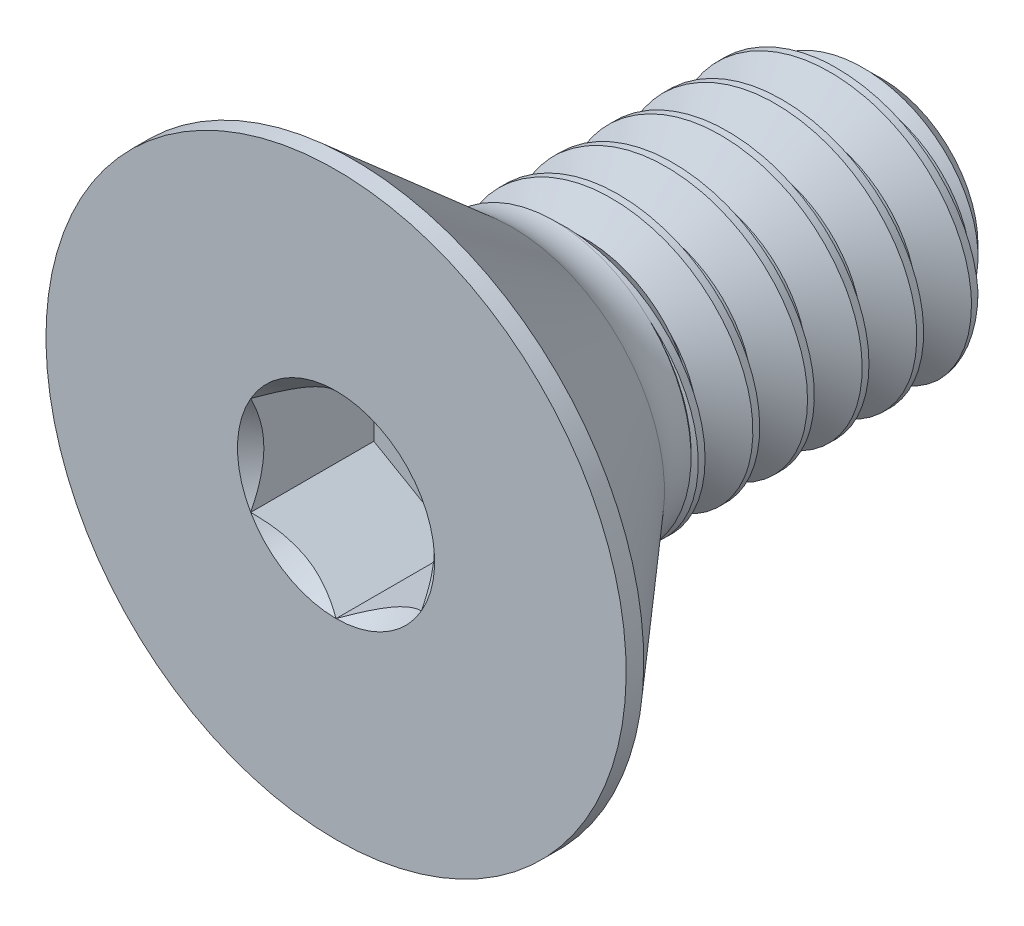
SolidWorks part; units mm, degrees
material "AISI 304"
ref_plane "Front" through (0, 0, 0) normal (0, 0, 1) x (1, 0, 0)
ref_plane "Top" through (0, 0, 0) normal (0, 1, 0) x (1, 0, 0)
ref_plane "Right" through (0, 0, 0) normal (1, 0, 0) x (0, 0, -1)
sketch "Sketch1" plane through (0, 0, 0) normal (1, 0, 0) x (0, 0, -1)
  line L0 (0, 6.7437) -> (0.4089, 6.7437) construction
  line L1 (0.4089, 6.7437) -> (4.0894, 3.5443) construction
  line L2 (0, 3.175) -> (12.7, 3.175)
  line L3 (12.7, 3.175) -> (12.7, 0)
  line L4 (12.7, 0) -> (0, 0)
  line L5 (0, 0) -> (0, 6.7437) construction
  line L6 (0, 6.7437) -> (0, -6.7437) construction
  line L7 (12.7, 3.175) -> (12.7, -3.175) construction
  line L8 (0, -6.7437) -> (0.4089, -6.7437) construction
  line L9 (0.4089, -6.7437) -> (4.0894, -3.5443) construction
  line L11 (0, 3.175) -> (0, 0)
  line L12 (5.0772, 3.175) -> (5.0772, 0) construction
  arc A1 (4.0894, 3.5443) -> (5.0772, 3.175) centre (5.0772, 4.6807) ccw construction
  dimension "D1" = 0.4089
revolve "Revolve1" add sketch "Sketch1" angle 360 mid plane about L4
sketch "Sketch3" plane through (0, 0, -12.7) normal (0, 0, -1) x (-1, 0, 0)
  circle A0 centre (0, 0) radius 3.175
curve "Helix/Spiral1" pitch 1.27 height 12.7 radius 3.175 centre (0, 0, -12.7) axis (0, 0, 1) start towards (0, 1, 0)
sketch "Sketch2" plane through (0, 0, 0) normal (1, 0, 0) x (0, 0, -1)
  line L0 (12.7, 3.175) -> (13.8113, 3.175)
  line L1 (13.8113, 3.175) -> (13.335, 2.3501)
  line L2 (13.335, 2.3501) -> (13.1762, 2.3501)
  line L3 (13.1762, 2.3501) -> (12.7, 3.175)
  line L4 (12.9381, 2.7626) -> (13.5731, 2.7626) construction
  dimension "D1" = 60
  dimension "D2" = 0.1588
  dimension "D3" = 0.635
chamfer "Chamfer1" distance 0.9525 angle 45 1 edges at (0, 3.175, -12.7)
sweep "Cut-Sweep1" cut profiles "Sketch2" path "Helix/Spiral1" align with end faces yes
sketch "Sketch7" plane through (0, 0, 0) normal (1, 0, 0) x (0, 0, -1)
  line L0 (0, 6.7437) -> (0.4089, 6.7437) construction
  line L1 (0.4089, 6.7437) -> (4.0894, 3.5443) construction
  line L2 (0, 6.7437) -> (0.4089, 6.7437)
  line L3 (0.4089, 6.7437) -> (4.0894, 3.5443)
  line L4 (5.0772, 3.175) -> (5.0772, 0) construction
  line L5 (5.0772, 3.175) -> (5.0772, 0)
  line L7 (0, 0) -> (0, 6.7437) construction
  line L8 (0, 0) -> (0, 6.7437)
  line L9 (0, 0) -> (5.0772, 0)
  line L10 (7.4181, 0) -> (-7.4181, 0) construction
  arc A0 (4.0894, 3.5443) -> (5.0772, 3.175) centre (5.0772, 4.6807) ccw construction
  arc A1 (4.0894, 3.5443) -> (5.0772, 3.175) centre (5.0772, 4.6807) ccw
revolve "Revolve2" add sketch "Sketch7" angle 360 mid plane about L9
ref_plane "Plane1" through (0, 0, -5.0772) normal (0, 0, 1) x (1, 0, 0)
sketch "Sketch8" plane through (0, 0, -5.0772) normal (0, 0, 1) x (1, 0, 0)
  circle A0 centre (0, 0) radius 3.175
extrude "Boss-Extrude1" add sketch "Sketch8" against normal through all draft 45
sketch "Sketch11" [suppressed] plane through (0, 0, 0) normal (1, 0, 0) x (0, 0, -1)
  line L0 (4.4996, 0) -> (-4.4996, 0) construction
  line L1 (7.3025, 3.8989) -> (1.7272, 3.8989)
  line L2 (7.3025, 3.8989) -> (7.3025, -3.8989)
  line L3 (7.3025, -3.8989) -> (1.7272, -3.8989)
  line L4 (1.7272, 3.8989) -> (1.7272, -3.8989)
  line L5 (0, 3.8989) -> (0.1727, 3.8989) construction
  line L7 (4.7625, 1.7526) -> (4.7625, 0) construction
  point P4 (1.7272, 0)
  dimension "D1" = 2.54
extrude "Cut-Extrude4" [suppressed] cut sketch "Sketch11" against normal through all and the other way through all
combine bodies "Combine1" operation type add bodies to combine 117 114
sketch "Sketch5" plane through (0, 0, 0) normal (0, 0, 1) x (1, 0, 0)
  line L1 (1.9844, -1.1457) -> (1.9844, 1.1457)
  line L2 (1.9844, 1.1457) -> (0, 2.2914)
  line L3 (0, 2.2914) -> (-1.9844, 1.1457)
  line L4 (-1.9844, 1.1457) -> (-1.9844, -1.1457)
  line L5 (-1.9844, -1.1457) -> (0, -2.2914)
  line L6 (0, -2.2914) -> (1.9844, -1.1457)
  circle A0 centre (0, 0) radius 1.9844 construction
  dimension "Hex" = 3.9688
extrude "Cut-Extrude2" cut sketch "Sketch5" against normal blind 2.8626
sketch "Sketch6" plane through (0, 0, 0) normal (0, 0, 1) x (1, 0, 0)
  circle A0 centre (0, 0) radius 2.2914
extrude "Cut-Extrude3" cut sketch "Sketch6" against normal blind 2.8626 draft 45
sketch "Sketch9" [suppressed] plane through (0, 0, -5.0772) normal (0, 0, 1) x (1, 0, 0)
  circle A1 centre (0, 0) radius 3.175
  circle A2 centre (0, 0) radius 3.175
  point P0 (0, 3.175)
  dimension "D1" = 0
extrude "Boss-Extrude2" [suppressed] add sketch "Sketch9" against normal offset from surface (20.3228 mm away) 44.45 up to face at (0, 2.2225, -12.7)
sketch "Sketch10" plane through (0, 0, 0) normal (1, 0, 0) x (0, 0, -1)
  line L0 (12.7, 3.175) -> (12.7, -3.175) construction
  point P0 (10.795, -3.175)
  dimension "D1" = 1.905
equation "\"D3@Helix/Spiral1\" = \"Lg@Sketch1\""
equation "\"D2@Sketch2\" = \"D4@Helix/Spiral1\" * .125"
equation "\"D3@Sketch2\" = \"D4@Helix/Spiral1\" * .5"
equation "\"D1@Chamfer1\" = \"D4@Helix/Spiral1\" * .75"
equation "\"D1@Cut-Extrude2\" = \"Head Ht@Sketch1\" * .7"
equation "\"D1@Sketch1\" = \"Head Ht@Sketch1\" * .1"
equation "\"D1@Sketch10\" = \"D4@Helix/Spiral1\" * 1.5"
equation "\"D1@Cut-Extrude3\" = \"D1@Cut-Extrude2\""
